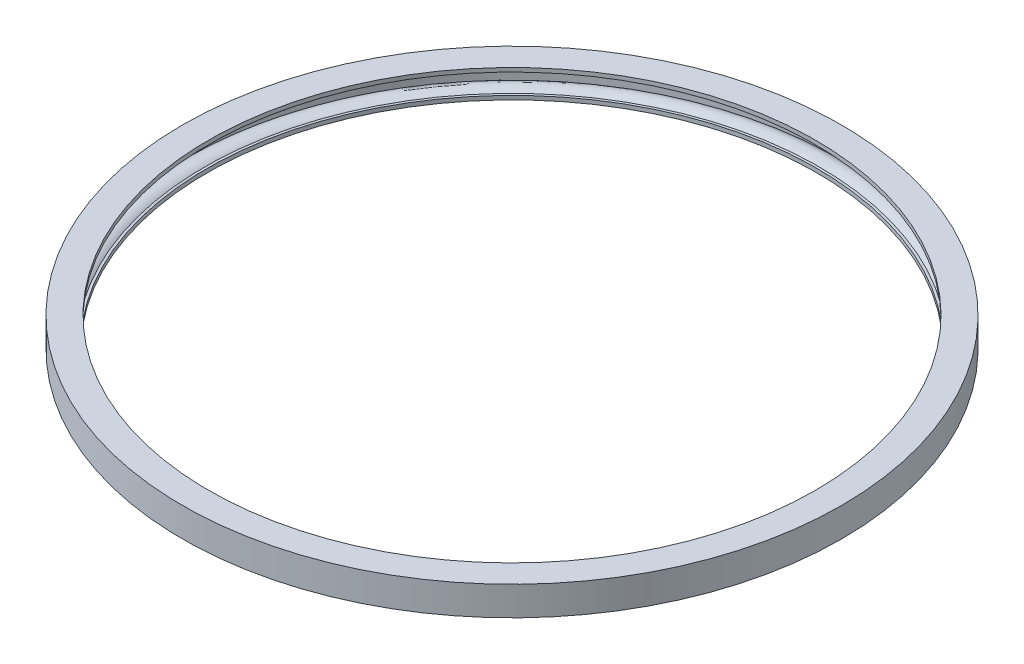
SolidWorks part; units mm, degrees
ref_plane "Front" through (0, 0, 0) normal (0, 0, 1) x (1, 0, 0)
ref_plane "Top" through (0, 0, 0) normal (0, 1, 0) x (1, 0, 0)
ref_plane "Right" through (0, 0, 0) normal (1, 0, 0) x (0, 0, -1)
sketch "Sketch2" plane through (19.1209, -245.3933, 65.5706) normal (0.1986, 0, -0.9801) x (-0.9801, 0, -0.1986)
  line L0 (-263.3326, 5.2216) -> (390.7174, 5.2216) construction
  line L1 (-263.3326, 5.2216) -> (63.6924, 5.2216) construction
  line L2 (-253.8076, 8.9005) -> (-253.8076, -16.4995)
  line L3 (-272.8576, 8.9005) -> (-272.8576, -16.4995)
  line L4 (-249.8076, 7.1619) -> (-249.8076, 11.2216)
  line L5 (-249.8076, 11.2216) -> (-219.5385, 11.2216)
  line L6 (-219.5385, 11.2216) -> (-276.8576, 11.2216)
  line L7 (-276.8576, 11.2216) -> (-276.8576, -18.8205)
  line L8 (-276.8576, -18.8205) -> (-251.2782, -18.8205)
  line L9 (-251.2782, -18.8205) -> (-251.2782, -14.7608)
  line L10 (-272.8576, -3.7995) -> (-253.8076, -3.7995) construction
  line L11 (-263.3326, -3.7995) -> (-263.3326, -18.8205) construction
  line L12 (-263.3326, -3.7995) -> (-263.3326, 11.2216) construction
  line L13 (-251.2782, -14.7608) -> (-253.8076, -14.7608)
  line L14 (-249.8076, 7.1619) -> (-253.8076, 7.1619)
  line L15 (63.6924, 5.2216) -> (63.6924, 39.475) construction
  line L16 (63.6924, -18.7995) -> (63.6924, 49.1889) construction
  arc A0 (-263.3326, -12.8205) -> (-272.8576, -16.4995) centre (-263.3326, -26.9903) ccw construction
  arc A1 (-253.8076, -16.4995) -> (-263.3326, -12.8205) centre (-263.3326, -26.9903) ccw construction
  arc A2 (-263.3326, 5.2216) -> (-253.8076, 8.9005) centre (-263.3326, 19.3914) ccw construction
  arc A3 (-272.8576, 8.9005) -> (-263.3326, 5.2216) centre (-263.3326, 19.3914) ccw construction
  arc A4 (-263.3326, -12.8205) -> (-272.8576, -16.4995) centre (-263.3326, -26.9903) ccw
  arc A5 (-253.8076, -16.4995) -> (-263.3326, -12.8205) centre (-263.3326, -26.9903) ccw
  arc A6 (-263.3326, 5.2216) -> (-253.8076, 8.9005) centre (-263.3326, 19.3914) ccw
  arc A7 (-272.8576, 8.9005) -> (-263.3326, 5.2216) centre (-263.3326, 19.3914) ccw
  dimension "D1" = 4
  dimension "D2" = 6
  dimension "D3" = 4
revolve "Revolve1" add sketch "Sketch2" angle 360 about L15 region at (272.3478, -238.8429, 116.8797)
